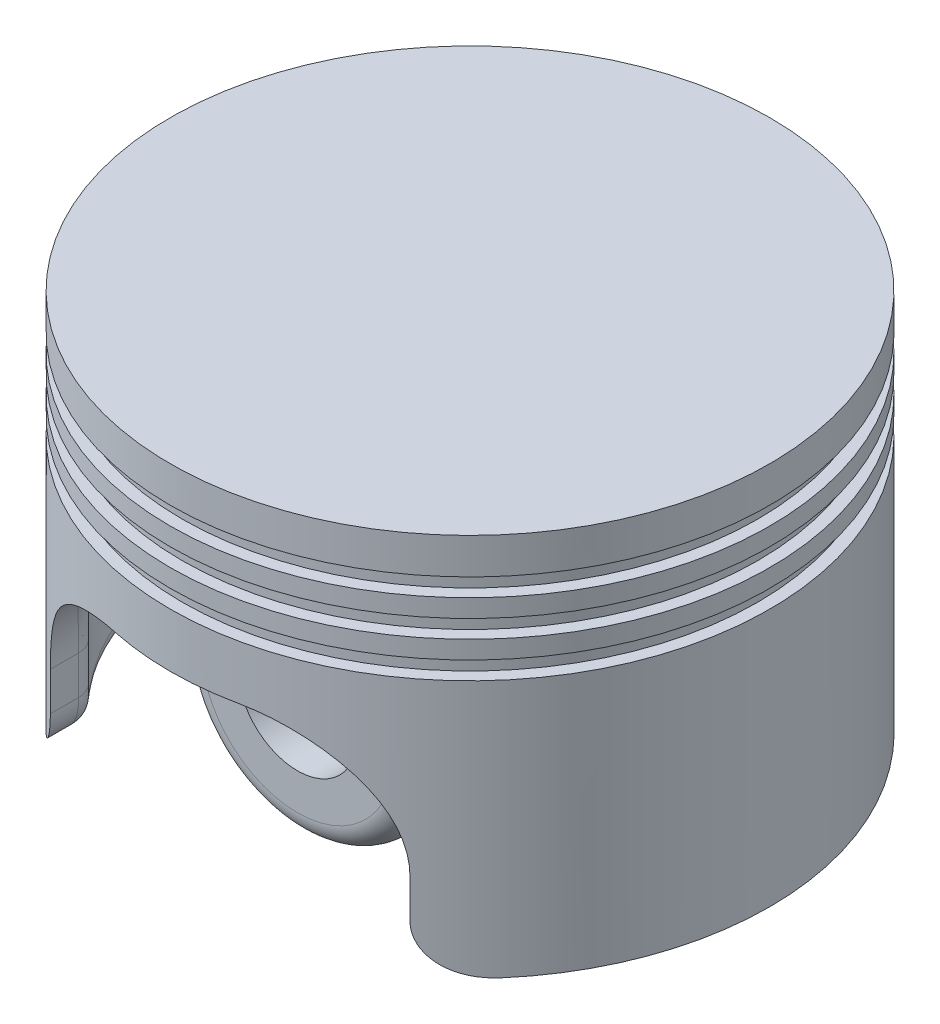
SolidWorks part; units mm, degrees
ref_plane "Front Plane" through (0, 0, 0) normal (0, 0, 1) x (1, 0, 0)
ref_plane "Top Plane" through (0, 0, 0) normal (0, 1, 0) x (1, 0, 0)
ref_plane "Right Plane" through (0, 0, 0) normal (1, 0, 0) x (0, 0, -1)
sketch "Sketch1" plane through (0, 0, 0) normal (0, 0, 1) x (1, 0, 0)
  line L0 (0, 0) -> (63.5, 0)
  line L1 (63.5, 0) -> (63.5, -81.28)
  line L2 (63.5, -81.28) -> (57.15, -81.28)
  line L3 (57.15, -81.28) -> (57.15, -19)
  line L4 (57.15, -19) -> (0, -19)
  line L5 (0, -19) -> (0, 0)
  dimension "D1" = 63.5
  dimension "D2" = 81.28
  dimension "D3" = 6.35
  dimension "D4" = 19
revolve "Revolve1" add sketch "Sketch1" angle 360 about L5
sketch "Sketch3" plane through (0, 0, 0) normal (0, 0, 1) x (1, 0, 0)
  line L0 (63.5, 0) -> (-63.5, 0) construction
  line L1 (60.96, -7.62) -> (63.5, -7.62)
  line L2 (60.96, -7.62) -> (60.96, -11.43)
  line L3 (60.96, -11.43) -> (63.5, -11.43)
  line L4 (63.5, -7.62) -> (63.5, -11.43)
  dimension "D1" = 7.62
  dimension "D2" = 3.81
  dimension "D3" = 2.54
  dimension "D4" = 63.5
ref_axis "Axis1" through (0, 0, 0) along (0, -1, 0)
revolve "Cut-Revolve1" cut sketch "Sketch3" angle 360 about axis through (0, 0, 0) along (0, -1, 0)
pattern_linear "LPattern1" count 3 spacing 7.62 along (0, -1, 0) of "Cut-Revolve1"
sketch "Sketch4" plane through (0, 0, 0) normal (0, 0, 1) x (1, 0, 0)
  line L0 (-57.15, -81.28) -> (57.15, -81.28) construction
  line L1 (-38.1, -81.3105) -> (38.1, -81.3105)
  line L2 (-38.1, -81.3105) -> (-38.1, -38.1)
  line L3 (-38.1, -38.1) -> (38.1, -38.1)
  line L4 (38.1, -81.3105) -> (38.1, -38.1)
  line L5 (-38.1, -81.28) -> (38.1, -81.28)
  line L6 (0, 0) -> (0, -81.28) construction
  line L7 (63.5, 0) -> (-63.5, 0) construction
  point P6 (0, -81.3105)
  dimension "D1" = 76.2
  dimension "D2" = 38.1
extrude "Cut-Extrude1" cut sketch "Sketch4" against normal through all both and the other way through all contours L2 L5 L4 L3 region at (0, -59.69, 0)
fillet "Fillet1" radius 25 4 edges at (-38.1, -38.1, 46.6985) (-38.1, -38.1, -46.6985) (38.1, -38.1, -46.6985) (38.1, -38.1, 46.6985)
fillet "Fillet2" radius 10 4 edges at (-38.1, -81.28, 46.6985) (-38.1, -81.28, -46.6985) (38.1, -81.28, -46.6985) (38.1, -81.28, 46.6985)
sketch "Sketch5" plane through (0, -19, 0) normal (0, -1, 0) x (1, 0, 0)
  line L0 (0, 0) -> (-42.2687, 0) construction
  line L1 (25.4, -17.55) -> (25.4, -36.55)
  line L2 (25.4, -17.55) -> (-25.4, -17.55)
  line L3 (-25.4, -17.55) -> (-25.4, -36.55)
  line L4 (25.4, -36.55) -> (-25.4, -36.55)
  line L5 (-17.55, -25.4) -> (-36.55, 25.4) construction
  line L6 (-17.55, 25.4) -> (-36.55, -25.4) construction
  line L7 (-25.4, 17.55) -> (-25.4, 36.55)
  line L8 (25.4, 36.55) -> (-25.4, 36.55)
  line L9 (25.4, 17.55) -> (25.4, 36.55)
  line L10 (25.4, 17.55) -> (-25.4, 17.55)
  point P0 (-27.05, 0)
  dimension "D1" = 19
  dimension "D2" = 50.8
  dimension "D3" = 17.55
extrude "Boss-Extrude1" add sketch "Sketch5" along normal blind 63.5 contours L4 L1 L2 L3 | L10 L9 L8 L7 region at (0, -19, -27.05) region at (0, -19, 27.05)
fillet "Fillet3" 2 edges at (-25.4, -82.5, -27.05) (25.4, -82.5, -27.05) type full round first side face at (-25.4, -50.75, -27.05) second side face at (25.4, -50.75, -27.05) middle face at (0, -82.5, -27.05)
fillet "Fillet4" 2 edges at (-25.4, -82.5, 27.05) (25.4, -82.5, 27.05) type full round first side face at (-25.4, -50.75, 27.05) second side face at (25.4, -50.75, 27.05) middle face at (0, -82.5, 27.05)
sketch "Sketch6" plane through (0, 0, -36.55) normal (0, 0, -1) x (-1, 0, 0)
  line L0 (0, 0) -> (0, -81.28) construction
  circle A0 centre (0, -57.1) radius 12.7
  point P6 (0, 0)
  dimension "D1" = 25.4
extrude "Cut-Extrude2" cut sketch "Sketch6" against normal up to surface (73.1 mm away) up to face at (0, -44.4, 36.55)
fillet "Fillet5" radius 5 16 edges at (39.4335, -76.2692, -41.3657) (38.1, -67.19, -42.5971) (28.4419, -43.3611, -49.5699) (0, -38.1, -57.15) (-34.33, -49.8982, -45.69) (-38.1, -67.19, -42.5971) (-40.816, -78.1316, -40.0022) (-57.15, -81.28, 0) (-39.4335, -76.2692, 41.3657) (-38.1, -67.19, 42.5971) (-28.4419, -43.3611, 49.5699) (0, -38.1, 57.15) (34.33, -49.8982, 45.69) (38.1, -67.19, 42.5971) (40.816, -78.1316, 40.0022) (57.15, -81.28, 0)
fillet "Fillet6" radius 5 10 edges at (-25.4, -19, 27.05) (25.4, -19, 27.05) (25.4, -38.05, 17.55) (-25.4, -38.05, 17.55) (-25.4, -38.05, 36.55) (25.4, -38.05, 36.55) (0, -82.5, 17.55) (0, -19, 17.55) (0, -19, 36.55) (0, -82.5, 36.55)
fillet "Fillet7" radius 5 10 edges at (0, -19, -36.55) (25.4, -19, -27.05) (-25.4, -19, -27.05) (25.4, -38.05, -36.55) (-25.4, -38.05, -36.55) (25.4, -38.05, -17.55) (0, -82.5, -17.55) (0, -82.5, -36.55) (0, -19, -17.55) (-25.4, -38.05, -17.55)
fillet "Fillet8" radius 5 1 edges at (0, -19, -57.15)
